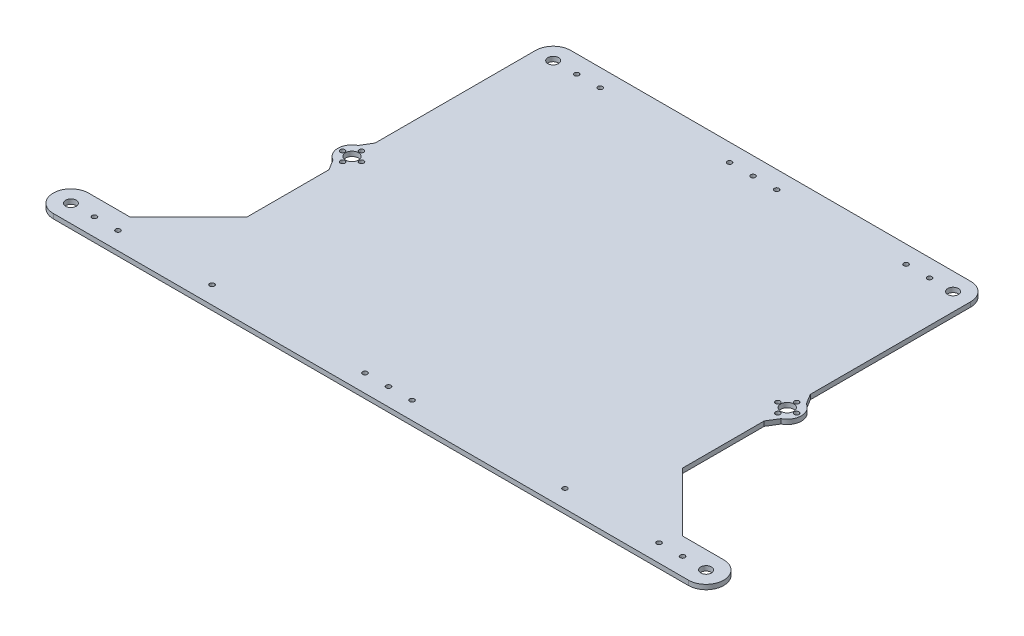
SolidWorks part; units mm, degrees
ref_plane "Front Plane" through (0, 0, 0) normal (0, 0, 1) x (1, 0, 0)
ref_plane "Top Plane" through (0, 0, 0) normal (0, 1, 0) x (1, 0, 0)
ref_plane "Right Plane" through (0, 0, 0) normal (1, 0, 0) x (0, 0, -1)
sketch "Sketch1" plane through (0, 0, 0) normal (0, 1, 0) x (1, 0, 0)
  line L0 (-170, 0) -> (170, 0) construction
  line L1 (-170, 0) -> (-270, 0) construction
  line L2 (-170, 310) -> (170, 310) construction
  line L3 (170, 0) -> (270, 0) construction
  line L4 (-270, 15) -> (-235, 15)
  line L5 (-185, 65) -> (-185, 142)
  line L6 (-170, 325) -> (170, 325)
  line L7 (185, 310) -> (185, 166)
  line L8 (235, 15) -> (270, 15)
  line L9 (270, -15) -> (-270, -15)
  line L10 (-235, 15) -> (-185, 65)
  line L11 (185, 65) -> (235, 15)
  line L12 (0, 0) -> (0, 310) construction
  line L14 (-185, 166) -> (-185, 310)
  line L15 (185, 142) -> (185, 65)
  circle A0 centre (-170, 310) radius 4.5
  circle A1 centre (170, 310) radius 4.5
  circle A2 centre (-270, 0) radius 4.5
  circle A3 centre (270, 0) radius 4.5
  circle A4 centre (0, 310) radius 2
  circle A5 centre (-150, 310) radius 2
  circle A6 centre (150, 310) radius 2
  circle A7 centre (0, 0) radius 2
  circle A8 centre (-150, 0) radius 2
  circle A9 centre (150, 0) radius 2
  arc A10 (-185, 310) -> (-170, 325) centre (-170, 310) cw
  arc A11 (170, 325) -> (185, 310) centre (170, 310) cw
  arc A12 (270, 15) -> (270, -15) centre (270, 0) cw
  arc A13 (-270, -15) -> (-270, 15) centre (-270, 0) cw
  circle A14 centre (-185, 154) radius 5.5
  circle A15 centre (-185, 162) radius 2
  circle A16 centre (-177, 154) radius 2
  circle A17 centre (-185, 146) radius 2
  circle A18 centre (-193, 154) radius 2
  arc A19 (-185, 166) -> (-185, 142) centre (-185, 154) ccw
  circle A20 centre (185, 162) radius 2
  circle A21 centre (177, 154) radius 2
  circle A22 centre (185, 146) radius 2
  circle A23 centre (193, 154) radius 2
  arc A24 (185, 166) -> (185, 142) centre (185, 154) cw
  circle A25 centre (185, 154) radius 5.5
  circle A26 centre (-130, 310) radius 2
  circle A27 centre (130, 310) radius 2
  circle A28 centre (-20, 310) radius 2
  circle A29 centre (20, 310) radius 2
  circle A30 centre (-250, 0) radius 2
  circle A31 centre (-230, 0) radius 2
  circle A32 centre (-20, 0) radius 2
  circle A33 centre (20, 0) radius 2
  circle A34 centre (230, 0) radius 2
  circle A35 centre (250, 0) radius 2
  point P25 (-185, 15)
  point P34 (185, 15)
  dimension "D2" = 9
  dimension "D6" = 4
  dimension "D11" = 11
  dimension "D12" = 4
  dimension "D19" = 12
  dimension "D21" = 15
  dimension "D22" = 15
  dimension "D1" = 310
  dimension "D3" = 340
  dimension "D4" = 340
  dimension "D5" = 100
  dimension "D7" = 150
  dimension "D8" = 150
  dimension "D9" = 150
  dimension "D10" = 150
  dimension "D15" = 16
  dimension "D16" = 16
  dimension "D17" = 8
  dimension "D18" = 8
  dimension "D20" = 0
  dimension "D23" = 20
  dimension "D24" = 20
  dimension "D25" = 20
  dimension "D26" = 20
  dimension "D27" = 20
  dimension "D28" = 20
  dimension "D29" = 20
extrude "Boss-Extrude1" add sketch "Sketch1" along normal blind 4
chamfer "Chamfer1" distance 10 angle 45 2 edges at (-185, 2, -142) (-185, 2, -166)
chamfer "Chamfer2" distance 10 angle 45 2 edges at (185, 2, -142) (185, 2, -166)
